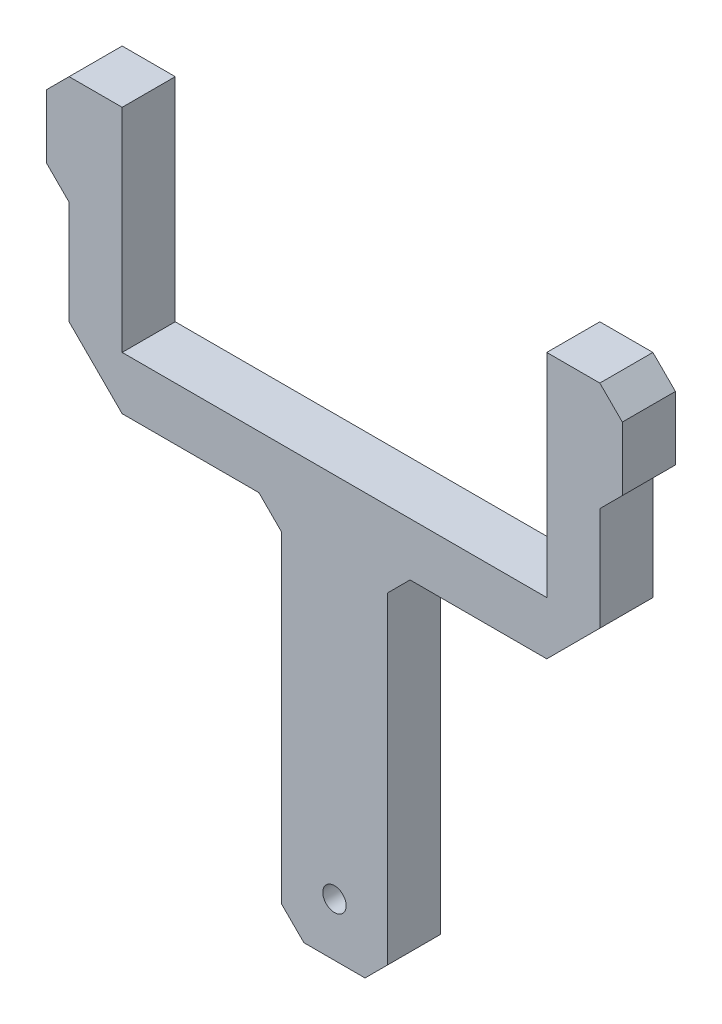
SolidWorks part; units mm, degrees
ref_plane "Alzado" through (0, 0, 0) normal (0, 0, 1) x (1, 0, 0)
ref_plane "Planta" through (0, 0, 0) normal (0, 1, 0) x (1, 0, 0)
ref_plane "Vista lateral" through (0, 0, 0) normal (1, 0, 0) x (0, 0, -1)
sketch "Croquis1" plane through (0, 0, 0) normal (0, 0, 1) x (1, 0, 0)
  line L0 (0, 0) -> (0, 44.6) construction
  line L1 (-5, 5) -> (5, 5)
  line L2 (-5, 5) -> (-5, -5)
  line L3 (-5, -5) -> (5, -5)
  line L4 (5, 5) -> (5, -5)
  line L5 (-5, 5) -> (5, -5) construction
  line L6 (-5, -5) -> (5, 5) construction
  line L7 (-20, 54.6) -> (-25, 54.6)
  line L8 (-20, 54.6) -> (20, 54.6)
  line L9 (-20, 54.6) -> (-20, 34.6)
  line L10 (-20, 34.6) -> (20, 34.6)
  line L12 (-20, 54.6) -> (20, 34.6) construction
  line L13 (-20, 34.6) -> (20, 54.6) construction
  line L18 (-25, 54.6) -> (-27.1213, 52.4787)
  line L19 (-27.1213, 52.4787) -> (-27.1213, 46.4787)
  line L20 (-27.1213, 46.4787) -> (-25, 44.3574)
  line L21 (-25, 44.3574) -> (-25, 34.5974)
  line L22 (20, 54.6) -> (20, 34.6)
  line L23 (-25, 34.5974) -> (-20.0026, 29.6)
  line L24 (-7.1213, 29.6) -> (-20.0026, 29.6)
  line L25 (-5, 27.4787) -> (-7.1213, 29.6)
  line L26 (-5, 5) -> (-5, 27.4787)
  line L27 (25, 44.3574) -> (25, 34.5974)
  line L28 (27.1213, 46.4787) -> (25, 44.3574)
  line L29 (25, 54.6) -> (27.1213, 52.4787)
  line L30 (27.1213, 52.4787) -> (27.1213, 46.4787)
  line L31 (20, 54.6) -> (25, 54.6)
  line L32 (25, 34.5974) -> (20.0026, 29.6)
  line L33 (7.1213, 29.6) -> (20.0026, 29.6)
  line L34 (5, 27.4787) -> (7.1213, 29.6)
  line L35 (5, 5) -> (5, 27.4787)
  circle A0 centre (0, 0) radius 1.1
  point P0 (0, 0)
  point P29 (-13.562, 29.6)
  dimension "D2" = 2.2
  dimension "D1" = 10
  dimension "D3" = 40
  dimension "D4" = 20
  dimension "D5" = 5
  dimension "D6" = 44.6
  dimension "D7" = 3
  dimension "D8" = 6
  dimension "D9" = 3
  dimension "D10" = 9.76
  dimension "D11" = 135
  dimension "D12" = 3
  dimension "D13" = 5
  dimension "D14" = 135
  dimension "D15" = 10
extrude "Saliente-Extruir1" add sketch "Croquis1" along normal blind 5 contours L9 | L10 L1 | L19 | L4 L1 L2 L3 A0 region at (0, 31.3456, 0) region at (0, 4.8586, 0)
sketch "Croquis2" plane through (0, 0, 0) normal (0, 0, -1) x (-1, 0, 0)
  line L0 (-5, -5) -> (-2.8787, -5)
  line L1 (5, -5) -> (-5, -5) construction
  line L2 (-2.8787, -5) -> (-5, -2.8787)
  line L3 (-5, -5) -> (-5, 27.4787) construction
  line L4 (-5, -2.8787) -> (-5, -5)
  line L5 (0, 55) -> (0, -55) construction
  line L6 (2.8787, -5) -> (5, -2.8787)
  line L7 (5, -5) -> (2.8787, -5)
  line L8 (5, -2.8787) -> (5, -5)
  dimension "D1" = 45
  dimension "D2" = 3
extrude "Cortar-Extruir1" cut sketch "Croquis2" against normal through all
